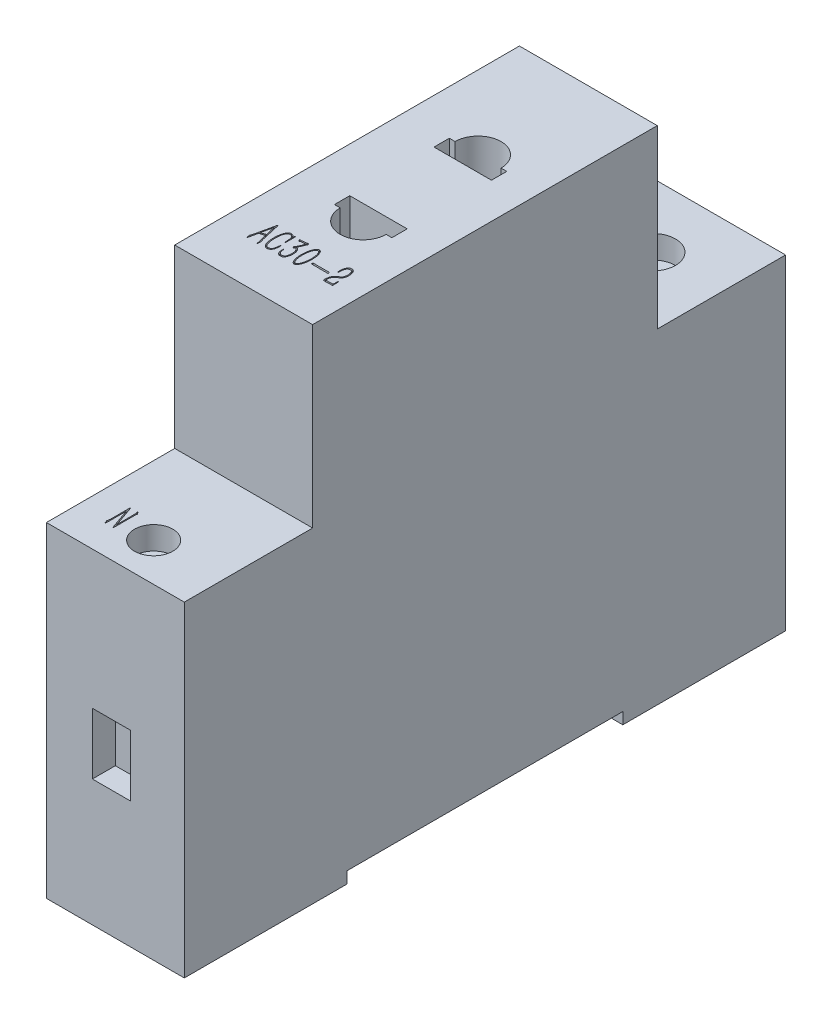
SolidWorks part; units mm, degrees
ref_plane "前视基准面" through (0, 0, 0) normal (0, 0, 1) x (1, 0, 0)
ref_plane "上视基准面" through (0, 0, 0) normal (0, 1, 0) x (1, 0, 0)
ref_plane "右视基准面" through (0, 0, 0) normal (1, 0, 0) x (0, 0, -1)
sketch "草图1" plane through (0, 0, 0) normal (1, 0, 0) x (0, 0, -1)
  line L0 (-22.5, 9.75) -> (-39.25, 9.75)
  line L1 (22.5, 32.75) -> (-22.5, 32.75)
  line L2 (22.5, 32.75) -> (22.5, 9.75)
  line L3 (22.5, -32.75) -> (18, -32.75)
  line L4 (-22.5, 32.75) -> (-22.5, 9.75)
  line L5 (22.5, 32.75) -> (-22.5, -32.75) construction
  line L6 (22.5, -32.75) -> (-22.5, 32.75) construction
  line L7 (39.25, -32.75) -> (18, -32.75)
  line L8 (39.25, -32.75) -> (39.25, 9.75)
  line L9 (39.25, 9.75) -> (22.5, 9.75)
  line L10 (-39.25, -32.75) -> (-39.25, 9.75)
  line L11 (-18, -32.75) -> (-22.5, -32.75)
  line L12 (18, -31.25) -> (-18, -31.25)
  line L13 (18, -31.25) -> (18, -32.75)
  line L14 (-18, -32.75) -> (-39.25, -32.75)
  line L15 (-18, -31.25) -> (-18, -32.75)
  line L16 (22.5, -32.75) -> (39.25, -32.75)
  line L17 (-22.5, -32.75) -> (-39.25, -32.75)
  point P0 (0, 0)
  point P10 (0, -32.75)
  dimension "D1" = 45
  dimension "D2" = 65.5
  dimension "D3" = 42.5
  dimension "D4" = 78.5
  dimension "D5" = 16.75
  dimension "D6" = 36
extrude "凸台-拉伸1" add sketch "草图1" along normal mid plane 18 contours L15 L12 L13 L3 L7 L8 L9 L2 L1 L4 L0 L10 L14 L11 region at (0, -3.3922, 0)
sketch "草图2" plane through (0, 9.75, 0) normal (0, 1, 0) x (1, 0, 0)
  line L0 (9, -39.25) -> (-9, -39.25) construction
  line L1 (-9, -22.5) -> (-9, -39.25) construction
  circle A0 centre (0, -34.25) radius 2.5
  dimension "D1" = 5
  dimension "D3" = 9
  dimension "D2" = 5
extrude "切除-拉伸1" cut sketch "草图2" against normal blind 3
sketch "草图3" plane through (0, 0, 39.25) normal (0, 0, 1) x (1, 0, 0)
  line L0 (-9, -32.75) -> (-9, 9.75) construction
  line L1 (-3, -8.25) -> (2, -8.25)
  line L2 (-3, -8.25) -> (-3, -16.25)
  line L3 (-3, -16.25) -> (2, -16.25)
  line L4 (2, -8.25) -> (2, -16.25)
  line L5 (9, 9.75) -> (-9, 9.75) construction
  dimension "D1" = 5
  dimension "D2" = 8
  dimension "D3" = 6
  dimension "D4" = 18
extrude "切除-拉伸2" cut sketch "草图3" against normal blind 3
sketch "草图5" plane through (0, 9.75, 0) normal (0, 1, 0) x (1, 0, 0)
  circle A0 centre (0, 30.875) radius 3
  dimension "D1" = 6
extrude "切除-拉伸3" cut sketch "草图5" against normal blind 3
sketch "草图6" plane through (0, 0, -39.25) normal (0, 0, -1) x (-1, 0, 0)
  line L1 (-2.4489, -8.4358) -> (2.5511, -8.4358)
  line L2 (-2.4489, -8.4358) -> (-2.4489, -16.4358)
  line L3 (-2.4489, -16.4358) -> (2.5511, -16.4358)
  line L4 (2.5511, -8.4358) -> (2.5511, -16.4358)
  line L5 (-2.4489, -8.4358) -> (2.5511, -16.4358) construction
  line L6 (-2.4489, -16.4358) -> (2.5511, -8.4358) construction
  point P0 (0.0511, -12.4358)
  dimension "D1" = 5
  dimension "D2" = 8
extrude "切除-拉伸4" cut sketch "草图6" against normal blind 3
sketch "草图9" plane through (0, 32.75, 0) normal (0, 1, 0) x (1, 0, 0)
  text T0 "\r\n            \r\n\r\n\r\n\r\n\r\n  AC30-2"
extrude "切除-拉伸6" cut sketch "草图9" against normal blind 0.3
sketch "0_0_Point" plane through (0, 0, -36.25) normal (0, 0, -1) x (-1, 0, 0)
  point P0 (0, -12.4358)
sketch "草图13" plane through (0, 9.75, 0) normal (0, 1, 0) x (1, 0, 0)
  text T0 "\r\n\r\n  N    "
  text T1 "\r\n L"
extrude "切除-拉伸7" cut sketch "草图13" against normal blind 0.3
sketch "草图16" plane through (0, 32.75, 0) normal (0, 1, 0) x (1, 0, 0)
  line L0 (9, 22.5) -> (-9, 22.5) construction
  line L1 (-3.1489, 7.5) -> (-2.3989, 7.5)
  line L2 (-3.1489, 7.5) -> (-3.1489, 5.5)
  line L3 (-3.1489, 5.5) -> (4.3511, 5.5)
  line L4 (4.3511, 7.5) -> (4.3511, 5.5)
  line L5 (-3.1489, 7.5) -> (4.3511, 5.5) construction
  line L6 (-3.1489, 5.5) -> (4.3511, 7.5) construction
  line L7 (9, 22.5) -> (9, -22.5) construction
  line L8 (3.6011, 7.5) -> (4.3511, 7.5)
  arc A0 (3.6011, 7.5) -> (-2.3989, 7.5) centre (0.6011, 7.5) ccw
  point P0 (0.6011, 6.5)
  dimension "D5" = 6
  dimension "D1" = 15
  dimension "D2" = 2
  dimension "D3" = 7.5
  dimension "D4" = 4.6489
extrude "切除-拉伸9" cut sketch "草图16" against normal blind 5
mirror "镜向1" about plane through (0, 0, 0) normal (0, 0, 1) of "切除-拉伸9"
sketch "0_1_Point" plane through (0, 0, 36.25) normal (0, 0, 1) x (1, 0, 0)
  point P0 (0, -12.4358)
sketch "草图18" plane through (0, 27.75, 0) normal (0, 1, 0) x (1, 0, 0)
  point P0 (0.6011, 7.5)
  point P1 (0.6011, -7.5)
other "0_0" parameters "直径"=2, "端头长度"=2
ref_axis "基准轴1" through (0, -12.4358, -46.25) along (0, 0, 1)
other "0_1" parameters "直径"=2, "端头长度"=2
ref_axis "基准轴2" through (0, -12.4358, 46.25) along (0, 0, -1)
